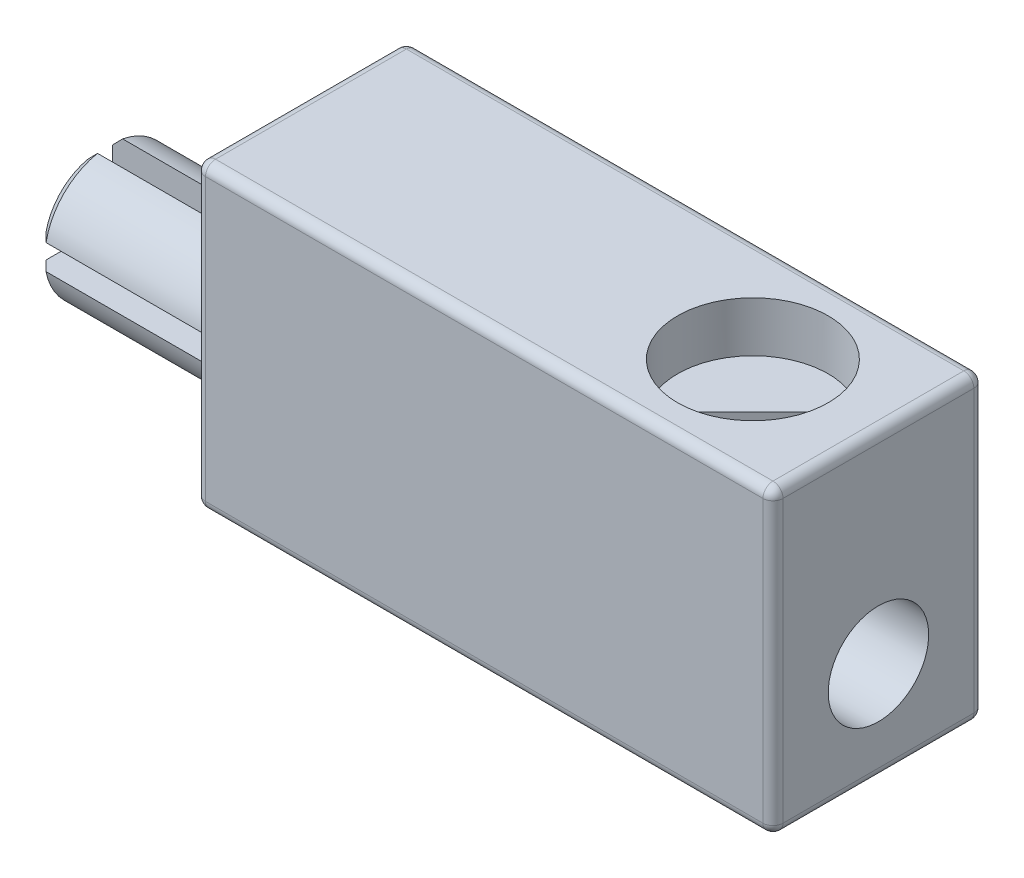
SolidWorks part; units mm, degrees
ref_plane "前视基准面" through (0, 0, 0) normal (0, 0, 1) x (1, 0, 0)
ref_plane "上视基准面" through (0, 0, 0) normal (0, 1, 0) x (1, 0, 0)
ref_plane "右视基准面" through (0, 0, 0) normal (1, 0, 0) x (0, 0, -1)
sketch "草图1" plane through (0, 0, 0) normal (0, 0, 1) x (1, 0, 0)
  line L1 (0, 0) -> (11.5, 0)
  line L2 (0, 0) -> (0, 6)
  line L3 (0, 6) -> (11.5, 6)
  line L4 (11.5, 0) -> (11.5, 6)
  dimension "D1" = 11.5
  dimension "D2" = 6
extrude "凸台-拉伸1" add sketch "草图1" along normal blind 4.2
sketch "草图2" plane through (0, 0, 0) normal (-1, 0, 0) x (0, 0, 1)
  line L0 (2.1, 0) -> (2.1, 2) construction
  line L1 (4.2, 0) -> (0, 0) construction
  circle A0 centre (2.1, 2) radius 1.5
  dimension "D2" = 3
  dimension "D1" = 2
extrude "切除-拉伸1" cut sketch "草图2" against normal blind 2
sketch "草图3" plane through (2, 0, 0) normal (-1, 0, 0) x (0, 0, 1)
  circle A0 centre (2.1, 2) radius 1.3
  dimension "D1" = 2.6
extrude "凸台-拉伸2" add sketch "草图3" along normal blind 6
chamfer "倒角1" distance 0.2 angle 45 1 edges at (-4, 2, 3.4)
sketch "草图4" plane through (-4, 0, 0) normal (-1, 0, 0) x (0, 0, 1)
  line L0 (2.1, 3.3) -> (2.1, 0.7) construction
  line L1 (0.8, 2) -> (3.4, 2) construction
  line L2 (1.85, 3.2757) -> (1.85, 2.25)
  line L3 (2.35, 3.2757) -> (2.35, 2.25)
  line L4 (0.8243, 1.75) -> (1.85, 1.75)
  line L5 (0.8243, 2.25) -> (1.85, 2.25)
  line L6 (2.35, 2.25) -> (3.3757, 2.25)
  line L7 (0.8, 2.25) -> (3.4, 2.25) construction
  line L8 (0.8, 1.75) -> (3.4, 1.75) construction
  line L9 (1.85, 3.3) -> (1.85, 0.7) construction
  line L10 (2.35, 3.3) -> (2.35, 0.7) construction
  line L11 (1.85, 1.75) -> (1.85, 0.7243)
  line L12 (2.35, 1.75) -> (3.3757, 1.75)
  line L13 (2.35, 1.75) -> (2.35, 0.7243)
  circle A0 centre (2.1, 2) radius 1.3 construction
  circle A1 centre (2.1, 2) radius 1.3 construction
  arc A2 (0.8243, 2.25) -> (0.8243, 1.75) centre (2.1, 2) ccw
  arc A3 (2.35, 3.2757) -> (1.85, 3.2757) centre (2.1, 2) ccw
  arc A4 (3.3757, 1.75) -> (3.3757, 2.25) centre (2.1, 2) ccw
  arc A5 (1.85, 0.7243) -> (2.35, 0.7243) centre (2.1, 2) ccw
  dimension "D1" = 0.25
  dimension "D2" = 0.25
  dimension "D3" = 0.25
  dimension "D4" = 0.25
extrude "切除-拉伸2" cut sketch "草图4" against normal blind 5
sketch "草图5" plane through (11.5, 0, 0) normal (1, 0, 0) x (0, 0, -1)
  line L0 (-2.1, 0) -> (-2.1, 2) construction
  line L1 (-4.2, 0) -> (0, 0) construction
  circle A0 centre (-2.1, 2) radius 1
  dimension "D2" = 2
  dimension "D1" = 2
extrude "切除-拉伸3" cut sketch "草图5" against normal blind 9
sketch "草图6" plane through (0, 0, 0) normal (0, -1, 0) x (1, 0, 0)
  line L0 (0, 2.1) -> (4.5, 2.1) construction
  line L1 (0, 4.2) -> (0, 0) construction
  circle A0 centre (4.5, 2.1) radius 1.3
  dimension "D2" = 2.6
  dimension "D1" = 4.5
extrude "切除-拉伸4" cut sketch "草图6" against normal blind 2
sketch "草图7" plane through (0, 6, 0) normal (0, 1, 0) x (1, 0, 0)
  line L0 (11.5, -2.1) -> (9, -2.1) construction
  line L1 (11.5, -4.2) -> (11.5, 0) construction
  circle A0 centre (9, -2.1) radius 1.5
  dimension "D2" = 3
  dimension "D1" = 2.5
extrude "切除-拉伸5" cut sketch "草图7" against normal blind 1
sketch "草图8" plane through (0, 5, 0) normal (0, 1, 0) x (1, 0, 0)
  line L0 (9, -2.1) -> (10.5, -2.1) construction
  line L1 (9, -2.1) -> (7.9393, -3.1607) construction
  line L2 (9, -2.1) -> (10.0607, -1.0393) construction
  line L3 (9.0884, -2.1884) -> (8.0314, -3.2454)
  line L4 (9.0884, -2.1884) -> (10.1454, -1.1314)
  line L5 (8.9116, -2.0116) -> (7.8546, -3.0686)
  line L6 (8.9116, -2.0116) -> (9.9686, -0.9546)
  line L8 (9.0884, -2.1884) -> (8.0277, -3.249) construction
  line L9 (8.9116, -2.0116) -> (7.851, -3.0723) construction
  line L10 (9.0884, -2.1884) -> (10.149, -1.1277) construction
  line L11 (8.9116, -2.0116) -> (9.9723, -0.951) construction
  circle A0 centre (9, -2.1) radius 1.5 construction
  circle A1 centre (9, -2.1) radius 1.5 construction
  arc A2 (7.8546, -3.0686) -> (8.0314, -3.2454) centre (9, -2.1) ccw
  arc A3 (10.1454, -1.1314) -> (9.9686, -0.9546) centre (9, -2.1) ccw
  dimension "D1" = 1.5
  dimension "D2" = 45
  dimension "D4" = 0.125
  dimension "D5" = 0.125
extrude "切除-拉伸6" cut sketch "草图8" against normal blind 0.5
sketch "草图9" plane through (0, 6, 0) normal (0, 1, 0) x (1, 0, 0)
  circle A0 centre (9, -2.1) radius 0.7
  dimension "D1" = 1.4
extrude "凸台-拉伸3" add sketch "草图9" against normal blind 1.6 from offset 3 offset against normal yes
fillet "圆角1" radius 0.2 12 edges at (0, 0, 2.1) (0, 3, 0) (5.75, 6, 0) (5.75, 0, 0) (11.5, 3, 0) (11.5, 0, 2.1) (11.5, 6, 2.1) (11.5, 3, 4.2) (5.75, 0, 4.2) (5.75, 6, 4.2) (0, 6, 2.1) (0, 3, 4.2)
